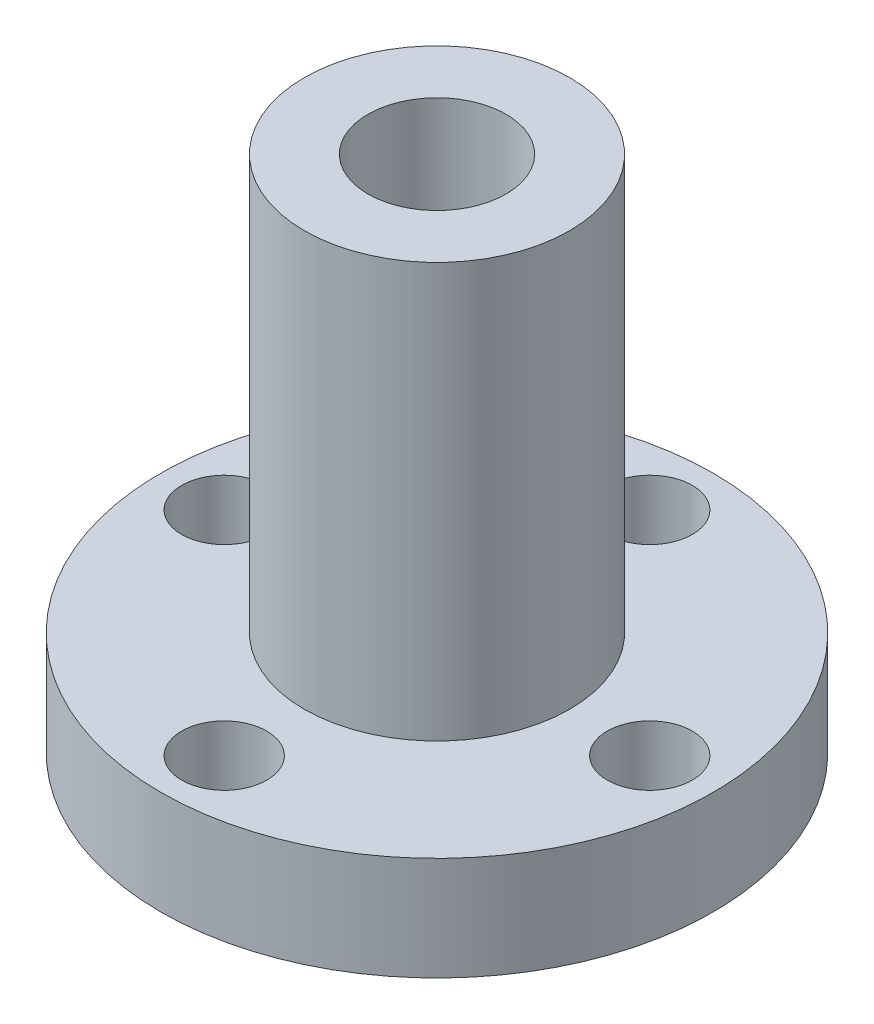
SolidWorks part; units mm, degrees
ref_plane "Front Plane" through (0, 0, 0) normal (0, 0, 1) x (1, 0, 0)
ref_plane "Top Plane" through (0, 0, 0) normal (0, 1, 0) x (1, 0, 0)
ref_plane "Right Plane" through (0, 0, 0) normal (1, 0, 0) x (0, 0, -1)
sketch "Sketch1" plane through (0, 0, 0) normal (0, 1, 0) x (1, 0, 0)
  circle A0 centre (0, 0) radius 12.7
  circle A1 centre (0, 9.779) radius 1.9558
  circle A2 centre (9.779, 0) radius 1.9558
  circle A3 centre (0, -9.779) radius 1.9558
  circle A4 centre (-9.779, 0) radius 1.9558
  circle A5 centre (0, 0) radius 6.096
  circle A6 centre (0, 0) radius 3.175
  circle A7 centre (0, 9.779) radius 3.302 construction
  circle A8 centre (0, 0) radius 13.081 construction
  point P14 (0, 0)
  dimension "D1" = 25.4
  dimension "D2" = 3.9116
  dimension "D5" = 12.192
  dimension "D6" = 6.35
  dimension "D7" = 6.604
  dimension "D3" = 9.779
  dimension "D4" = 4
extrude "Boss-Extrude1" add sketch "Sketch1" against normal blind 4.7625 contours A0 A5 A4 A3 A2 A1 | A5 A6 region at (-12.3408, 0, 0) region at (-5.9236, 0, 0)
extrude "Boss-Extrude2" add sketch "Sketch1<3>" along normal blind 19.05 contours A5 A6 region at (-5.9236, 0, 0)
sketch "Sketch1<3>" plane through (0, 0, 0) normal (0, 1, 0) x (1, 0, 0) same geometry as "Sketch1"
